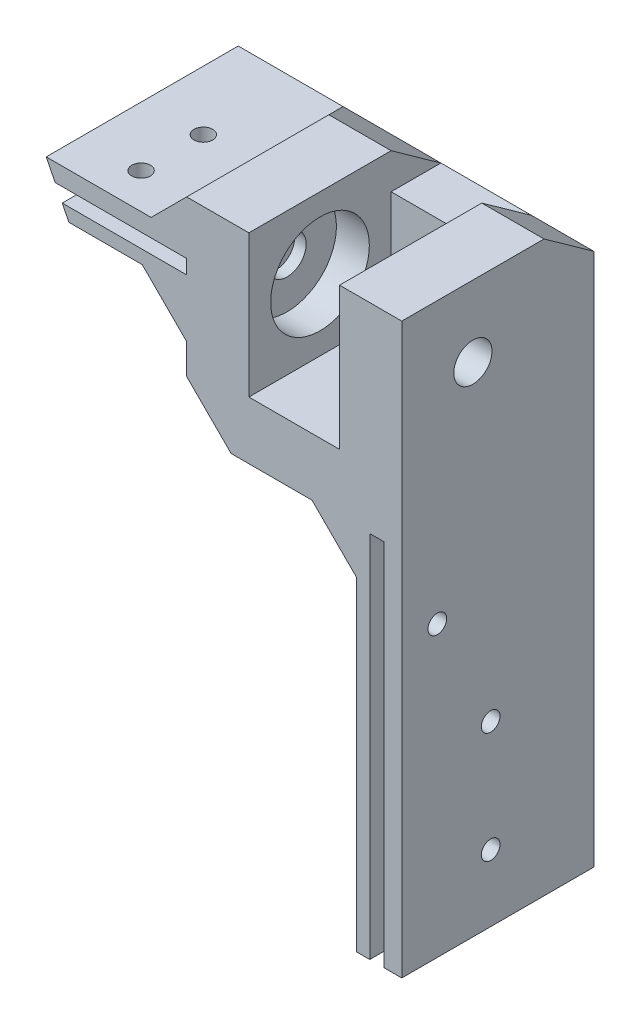
SolidWorks part; units mm, degrees
material "ABS"
ref_plane "Płaszczyzna przednia" through (0, 0, 0) normal (0, 0, 1) x (1, 0, 0)
ref_plane "Płaszczyzna górna" through (0, 0, 0) normal (0, 1, 0) x (1, 0, 0)
ref_plane "Płaszczyzna prawa" through (0, 0, 0) normal (1, 0, 0) x (0, 0, -1)
sketch "Szkic1" plane through (0, 0, 0) normal (0, 0, 1) x (1, 0, 0)
  line L0 (0, 0) -> (80, 0)
  line L1 (0, 0) -> (0, -120)
  line L2 (80, 0) -> (20, -120)
  line L3 (20, -120) -> (0, -120)
  dimension "D1" = 80
  dimension "D2" = 120
  dimension "D3" = 20
extrude "Dodanie-wyciągnięcie1" add sketch "Szkic1" along normal blind 4
sketch "Szkic2" plane through (0, 0, 4) normal (0, 0, 1) x (1, 0, 0)
  line L0 (80, 0) -> (0, 0) construction
  line L1 (0, 0) -> (0, -120) construction
  line L2 (80, 0) -> (0, 0)
  line L3 (0, 0) -> (0, -120)
  line L4 (78, -4) -> (4, -4)
  line L5 (4, -4) -> (4, -120)
  line L6 (4, -120) -> (0, -120)
  line L7 (80, 0) -> (78, -4)
  line L9 (80, -4) -> (4, -4) construction
  dimension "D1" = 4
extrude "Dodanie-wyciągnięcie2" add sketch "Szkic2" along normal blind 3.2
sketch "Szkic3" plane through (0, 0, 7.2) normal (0, 0, 1) x (1, 0, 0)
  line L0 (78, -4) -> (80, 0) construction
  line L1 (0, -120) -> (4, -120) construction
  line L2 (4, -120) -> (20, -120) construction
  line L3 (20, -120) -> (78, -4) construction
  line L4 (80, 0) -> (0, 0) construction
  line L5 (0, 0) -> (0, -120) construction
  line L6 (78, -4) -> (80, 0)
  line L7 (0, -120) -> (4, -120)
  line L8 (4, -120) -> (20, -120)
  line L9 (20, -120) -> (78, -4)
  line L10 (80, 0) -> (0, 0)
  line L11 (0, 0) -> (0, -120)
extrude "Dodanie-wyciągnięcie3" add sketch "Szkic3" along normal blind 4
sketch "Szkic4" plane through (0, 0, 11.2) normal (0, 0, 1) x (1, 0, 0)
  line L0 (0, 8) -> (0, -37)
  line L1 (0, 0) -> (0, -120) construction
  line L3 (14, -24) -> (14, 8)
  line L6 (34.4, -24) -> (34.4, 8)
  line L7 (80, 0) -> (0, 0) construction
  line L8 (48.4, 8) -> (48.4, -37)
  line L9 (0, 8) -> (14, 8)
  line L10 (34.4, 8) -> (48.4, 8)
  line L11 (0, -37) -> (48.4, -37)
  line L12 (14, -24) -> (34.4, -24)
  dimension "D1" = 45
  dimension "D2" = 14
  dimension "D3" = 20.4
  dimension "D4" = 14
  dimension "D5" = 8
  dimension "D6" = 32
extrude "Dodanie-wyciągnięcie4" add sketch "Szkic4" along normal blind 32
ref_plane "Płaszczyzna1" through (24.2, 0, 0) normal (1, 0, 0) x (0, 0, -1)
sketch "Szkic5" plane through (24.2, 0, 0) normal (1, 0, 0) x (0, 0, -1)
  line L0 (-11.2, -120) -> (-11.2, 0) construction
  line L1 (-43.2, 8) -> (-11.2, 8) construction
  circle A0 centre (-27.2, -8) radius 11.1
  dimension "D1" = 22.2
  dimension "D3" = 16
  dimension "D2" = 16
extrude "Wytnij-wyciągnięcie1" cut sketch "Szkic5" against normal blind 17.6 and the other way blind 17.6
chamfer "Sfazowanie1" distance 11.2 distance2 8 2 edges at (7, 0, 11.2) (41.4, 0, 11.2) first distance on face at (36.6857, 0, 8)
sketch "Szkic6" plane through (24.2, 0, 0) normal (1, 0, 0) x (0, 0, -1)
  circle A0 centre (-27.2, -8) radius 11.1 construction
  circle A1 centre (-27.2, -8) radius 11.1 construction
  circle A2 centre (-27.2, -8) radius 4.3
  dimension "D1" = 8.6
extrude "Wytnij-wyciągnięcie2" cut sketch "Szkic6" against normal through all and the other way blind 20.2
sketch "Szkic7" plane through (0, 0, 11.2) normal (0, 0, 1) x (1, 0, 0)
  line L0 (0, -37) -> (0, -120)
  line L1 (0, -120) -> (20, -120) construction
  line L2 (0, -37) -> (0, -120) construction
  line L3 (0, -120) -> (4, -120)
  line L4 (4, -120) -> (4, -37)
  line L5 (0, -37) -> (48.4, -37) construction
  line L6 (4, -37) -> (0, -37)
  line L11 (0, -37) -> (48.4, -37) construction
  line L12 (7.2, -37) -> (10.2, -37)
  line L13 (7.2, -37) -> (7.2, -120)
  line L14 (7.2, -120) -> (10.2, -120)
  line L15 (10.2, -37) -> (10.2, -120)
  line L16 (48.4, 0) -> (80, 0)
  line L17 (80, 0) -> (78, -4)
  line L18 (20, -120) -> (80, 0) construction
  line L19 (78, -4) -> (48.4, -4)
  line L20 (48.4, -37) -> (48.4, 0) construction
  line L21 (48.4, -4) -> (48.4, 0)
  line L22 (48.4, -7.2) -> (76.4, -7.2)
  line L23 (76.4, -7.2) -> (74.9, -10.2)
  line L24 (74.9, -10.2) -> (48.4, -10.2)
  line L25 (48.4, -10.2) -> (48.4, -7.2)
  dimension "D1" = 4
  dimension "D2" = 3
  dimension "D3" = 3.2
  dimension "D4" = 4
  dimension "D5" = 3
  dimension "D6" = 3.2
extrude "Dodanie-wyciągnięcie5" add sketch "Szkic7" along normal blind 32
chamfer "Sfazowanie2" distance 10 angle 45 3 edges at (48.4, -37, 27.2) (48.4, -10.2, 27.2) (10.2, -37, 27.2)
chamfer "Sfazowanie3" distance 2 angle 70 7 edges at (66.65, -10.2, 11.2) (53.4, -15.2, 11.2) (48.4, -23.6, 11.2) (43.4, -32, 11.2) (29.3, -37, 11.2) (15.2, -42, 11.2) (10.2, -83.5, 11.2) first distance on face at (36.5667, -47.6222, 11.2)
sketch "Szkic8" plane through (0, -10.2, 0) normal (0, -1, 0) x (1, 0, 0)
  line L0 (58.4, 43.2) -> (74.9, 43.2) construction
  line L1 (20, 11.2) -> (73.9, 11.2) construction
  line L2 (58.4, 43.2) -> (58.4, 16.695) construction
  circle A0 centre (66.65, 35.2) radius 2.1
  circle A1 centre (66.65, 21.2) radius 2.1
  dimension "D3" = 4.2
  dimension "D1" = 8
  dimension "D2" = 10
  dimension "D4" = 8.25
extrude "Otwory tyl" cut sketch "Szkic8" against normal through all
sketch "Szkic9" plane through (0, 0, 11.2) normal (0, 0, 1) x (1, 0, 0)
  line L0 (50.4, -21.0284) -> (50.4, -27.8284) construction
  line L1 (73.9, -12.2) -> (59.2284, -12.2) construction
  line L2 (12.2, -47.8284) -> (12.2, -120) construction
  line L3 (39.2284, -39) -> (21.0284, -39) construction
  circle A0 centre (60.4, -22.2) radius 3.1
  circle A1 centre (22.2, -49) radius 2.1
  circle A2 centre (22.2, -89) radius 2.1
  circle A3 centre (36.2, -49) radius 2.1
  dimension "D1" = 4.2
  dimension "D2" = 6.2
  dimension "D3" = 10
  dimension "D4" = 10
  dimension "D5" = 10
  dimension "D6" = 40
  dimension "D7" = 14
  dimension "D8" = 10
extrude "Otwory spod" cut sketch "Szkic9" against normal through all
sketch "Szkic10" plane through (10.2, 0, 0) normal (1, 0, 0) x (0, 0, -1)
  line L0 (-43.2, -120) -> (-43.2, -47) construction
  line L1 (-11.2, -47.8284) -> (-11.2, -120) construction
  line L2 (-16.695, -47) -> (-43.2, -47) construction
  circle A0 centre (-23.2, -80) radius 2.1
  circle A1 centre (-35.2, -55) radius 2.1
  circle A2 centre (-23.2, -105) radius 2.1
  dimension "D7" = 4.2
  dimension "D1" = 8
  dimension "D2" = 12
  dimension "D3" = 8
  dimension "D4" = 25
  dimension "D5" = 25
  dimension "D6" = 12
extrude "Otwory bok" cut sketch "Szkic10" against normal through all
chamfer "Sfazowanie4" distance 8 angle 45 1 edges at (48.4, 0, 21.6)
mirror "Lustro1" about plane through (0, 0, 4) normal (1, 0, 0) of bodies 110
sketch "Szkic11" plane through (0, -120, 0) normal (0, -1, 0) x (1, 0, 0)
  line L1 (0, 0) -> (89.6269, 0)
  line L2 (0, 0) -> (0, 50.5875)
  line L3 (0, 50.5875) -> (89.6269, 50.5875)
  line L4 (89.6269, 0) -> (89.6269, 50.5875)
extrude "Wytnij-wyciągnięcie3" cut sketch "Szkic11" against normal through all
